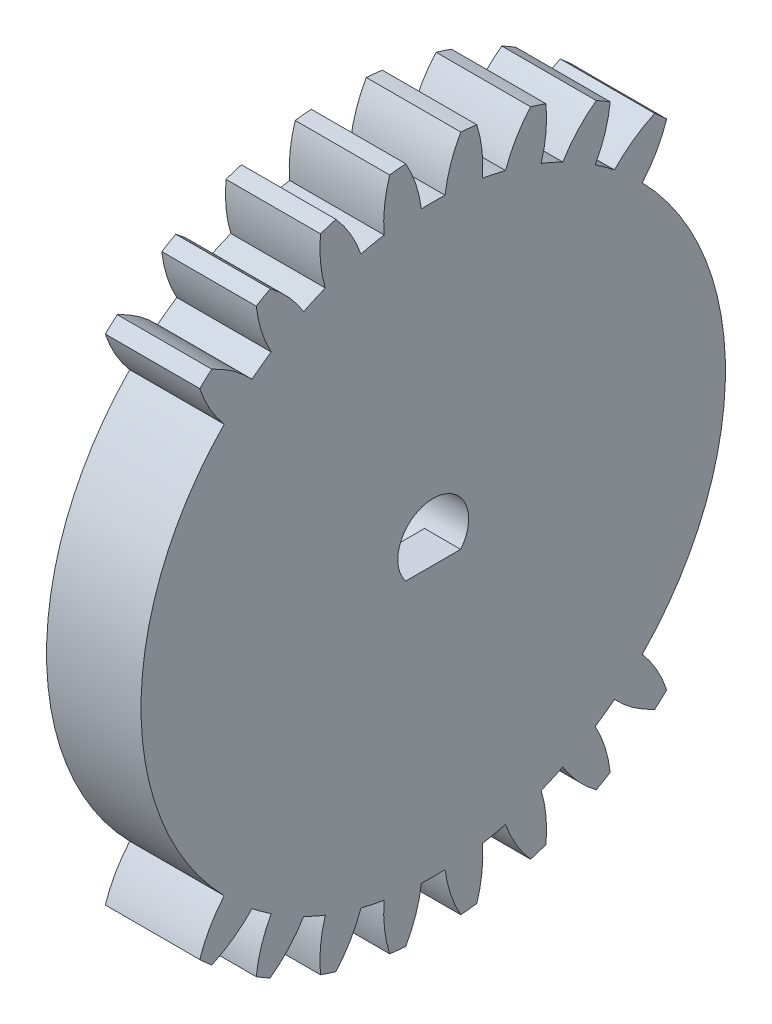
SolidWorks part; units mm, degrees
ref_plane "Plane1" through (0, 0, 0) normal (0, 0, 1) x (1, 0, 0)
ref_plane "Plane2" through (0, 0, 0) normal (0, 1, 0) x (1, 0, 0)
ref_plane "Plane3" through (0, 0, 0) normal (1, 0, 0) x (0, 0, -1)
other "Configuration Table"
sketch "HoldingSke" plane through (0, 0, 0) normal (0, 1, 0) x (1, 0, 0)
  line L0 (0, 0) -> (1.0373, -0.3982)
  line L1 (-15, 0) -> (100, 0) construction
  line L2 (0, 0) -> (-2.1039, 2.3779)
  line L3 (0, 0) -> (-11.863, 4.5341)
  line L4 (0, 0) -> (7.479, 4.318)
  line L5 (0, 0) -> (-46.8476, -17.4728)
  line L6 (0, 0) -> (-8.2896, -5.593)
  line L7 (-2.1039, 2.3779) -> (8.6586, 51.2059)
  line L8 (-76.2, 54.61) -> (-75.5, 54.61)
  line L9 (-67.7845, 28.3722) -> (-49.3413, 33.142)
  line L10 (-76.2, 71.12) -> (104.1128, 71.12)
  line L11 (0, 0) -> (-10, 0)
  line L12 (-76.2, 101.6) -> (-76.166, 101.6)
  line L13 (24.9733, 27.94) -> (52.9518, 28.4284)
  line L14 (24.9733, 27.94) -> (24.9743, 27.94)
  line L15 (24.9733, 27.94) -> (100.4006, 29.5858)
  line L16 (-63.627, -0.9) -> (-12.827, -0.9)
  circle A0 centre (0, 0) radius 2
  circle A1 centre (0, 0) radius 12.374
  circle A2 centre (0, 0) radius 37.5
  circle A3 centre (0, 0) radius 2
  dimension "Num_teeth" = 30
  dimension "Pitch_radius" = 180.3128
  dimension "Width" = 10
  dimension "Thickness" = 10
sketch "BasProSke" plane through (0, 0, 0) normal (0, 1, 0) x (1, 0, 0)
  line L0 (-10, 0) -> (60, 0) construction
  line L1 (0, 0) -> (0, 14.4)
  line L2 (0, 0) -> (4, 0)
  line L3 (4, 0) -> (4, 14.4)
  line L4 (4, 14.4) -> (0, 14.4)
  dimension "Diameter" = 28.8
  dimension "D1" = 4
revolve "Base-Revolve" add sketch "BasProSke" angle 360 about L0
sketch "TooCutSke" plane through (0, 0, 0) normal (1, 0, 0) x (0, 0, -1)
  line L1 (0, 0) -> (0, 107) construction
  line L2 (0, 0) -> (-0.766, 13.4782) construction
  line L3 (0, 0) -> (-2.819, 26.8212) construction
  line L4 (-0.766, 13.4782) -> (-1.4095, 13.4106) construction
  arc A0 (0.502, 12.3638) -> (-0.502, 12.3638) centre (0, 0) ccw
  arc A1 (1.1789, 14.3771) -> (-1.1789, 14.3771) centre (0, 0) ccw
  circle A2 centre (0, 0) radius 13.5 construction
  circle A3 centre (0, 0) radius 13.07 construction
  arc A4 (-0.502, 12.3638) -> (-1.1789, 14.3771) centre (-5.8589, 11.6832) ccw
  arc A5 (1.1789, 14.3771) -> (0.502, 12.3638) centre (5.8589, 11.6832) ccw
extrude "ToothCut" cut sketch "TooCutSke" along normal through all
fillet "Breaks" [suppressed] radius 0.018 tangent propagation no
fillet "RootFillets" [suppressed] radius 0.226
pattern_circular "TeethCuts" count 30 every 12 about axis through (-10, 0, 0) along (1, 0, 0) of "ToothCut"
sketch "HubNeaOneSke" plane through (0, 0, 0) normal (-1, 0, 0) x (0, 0, 1)
  circle A0 centre (0, 0) radius 12.374
  dimension "Diameter" = 24.748
extrude "HubNearOne" [suppressed] add sketch "HubNeaOneSke" along normal blind 40.0001
sketch "HubNeaBotSke" plane through (0, 0, 0) normal (-1, 0, 0) x (0, 0, 1)
  circle A0 centre (0, 0) radius 12.374
  dimension "Diameter" = 24.748
extrude "HubNearBoth" [suppressed] add sketch "HubNeaBotSke" along normal blind 20
ref_plane "FarPln" through (10, 0, 0) normal (1, 0, 0) x (0, 0, -1)
sketch "HubFarSke" plane through (10, 0, 0) normal (1, 0, 0) x (0, 0, -1)
  circle A0 centre (0, 0) radius 12.374
  dimension "Diameter" = 24.748
extrude "HubFar" [suppressed] add sketch "HubFarSke" along normal blind 20
sketch "BorSke" plane through (0, 0, 0) normal (1, 0, 0) x (0, 0, -1)
  line L0 (-1.1608, -0.95) -> (1.1608, -0.95)
  line L1 (0, 1.5) -> (0, -0.95) construction
  arc A0 (1.1608, -0.95) -> (-1.1608, -0.95) centre (0, 0) ccw
  dimension "D1" = 2.45
  dimension "Diameter" = 3
extrude "Bore" cut sketch "BorSke" along normal mid plane 100.0001
sketch "KeySke" plane through (0, 0, 0) normal (1, 0, 0) x (0, 0, -1)
  line L0 (-0.8, 0) -> (-0.8, 2.7)
  line L1 (-0.8, 2.7) -> (0.8, 2.7)
  line L2 (0.8, 2.7) -> (0.8, 0)
  line L3 (0, 0) -> (0, 34) construction
  line L4 (-0.8, 0) -> (0.8, 0)
  dimension "Width" = 1.6
extrude "Keyway" [suppressed] cut sketch "KeySke" along normal mid plane 100.0001
pattern_circular "Keyway2" [suppressed] count 2 every 90 about axis through (-10, 0, 0) along (1, 0, 0)
sketch "Sketch1" plane through (4, 0, 0) normal (1, 0, 0) x (0, 0, -1)
  line L4 (0, 12.374) -> (0, -12.374) construction
  line L9 (-9.1957, 8.2798) -> (-11.8374, 9.9904)
  line L10 (-9.0832, -8.4031) -> (-11.109, -10.7946)
  line L11 (9.0832, -8.4031) -> (11.109, -10.7946)
  line L12 (9.1957, 8.2798) -> (11.8374, 9.9904)
  arc A11 (0.502, 12.3638) -> (-0.502, 12.3638) centre (0, 0) ccw construction
  arc A12 (-0.502, -12.3638) -> (0.502, -12.3638) centre (0, 0) ccw construction
  arc A14 (-9.1957, 8.2798) -> (-9.0832, -8.4031) centre (0, 0) ccw
  arc A15 (-10.4564, 6.6167) -> (-10.9584, 5.7472) centre (0, 0) ccw construction
  arc A16 (-11.109, -10.7946) -> (-11.8374, 9.9904) centre (0, 0) cw
  arc A17 (-8.8522, 8.6461) -> (-9.524, 7.8999) centre (0, 0) ccw construction
  arc A18 (11.109, -10.7946) -> (11.8374, 9.9904) centre (0, 0) ccw
  arc A19 (9.1957, 8.2798) -> (9.0832, -8.4031) centre (0, 0) cw
  point P9 (0, 0)
  point P11 (-9.0832, -8.4031)
  point P13 (0, 0)
  point P20 (-10.9357, -10.59)
  point P21 (-9.1957, 8.2798)
  point P25 (-11.8374, 9.9904)
extrude "Cut-Extrude2" cut sketch "Sketch1" against normal blind 10
sketch "Sketch3" plane through (0, 0, 0) normal (-1, 0, 0) x (0, 0, 1)
  circle A2 centre (0, 0) radius 1.5
  dimension "D1" = 3
extrude "Cut-Extrude3" cut sketch "Sketch3" against normal blind 2.47
equation "' \"Module@HoldingSke\" = 6.35"
equation "' \"Num_teeth@HoldingSke\" = 12"
equation "' \"Ap@HoldingSke\" =  20"
equation "' \"Ap@HoldingSke\" = 20"
equation "' \"Width@HoldingSke\" = 0.5 * 25.4"
equation "' \"Hub_dia@HoldingSke\"= 1 * 25.4"
equation "' \"Hub_dia@HoldingSke\" = 1 * 25.4"
equation "' \"Overall_len@HoldingSke\" = 1.0 * 25.4"
equation "' \"Bore@HoldingSke\" = 0.75 * 25.4"
equation "' \"T_dim@HoldingSke\" = 0.1 * 25.4"
equation "' \"Width@KeySke\" = 0.25 * 25.4"
equation "' \"Show_teeth@HoldingSke\" = 13"
equation "' \"Backlash@HoldingSke\" = 0.009 * 25.4"
equation "' \"Addendum_fac@HoldingSke\" = 1.0"
equation "' \"Dedendum_fac@HoldingSke\" = 1.25"
equation "' \"Dedendum_add@HoldingSke\" = 0.00005 * 25.4"
equation "' \"Clearance_fac@HoldingSke\" = 0.25"
equation "\"Pitch@HoldingSke\" = 1 / \"Module@HoldingSke\""
equation "\"Overcut_dia@TooCutSke\" = (\"Num_teeth@HoldingSke\" + 2 * \"Addendum_fac@HoldingSke\") / \"Pitch@HoldingSke\" + 0.002 * 25.4"
equation "\"Pitch_dia@TooCutSke\" = \"Num_teeth@HoldingSke\" / \"Pitch@HoldingSke\""
equation "\"Base_dia@TooCutSke\" = \"Num_teeth@HoldingSke\" / \"Pitch@HoldingSke\" * cos((\"Ap@HoldingSke\"  * 3.14159265 / 180))"
equation "\"Root_dia@TooCutSke\" = (\"Num_teeth@HoldingSke\" + 2) / \"Pitch@HoldingSke\" - 2 * (\"Addendum_fac@HoldingSke\" + \"Dedendum_fac@HoldingSke\") / \"Pitch@HoldingSke\" - \"Dedendum_add@HoldingSke\" * 2"
equation "\"Half_ang@TooCutSke\" = 180 / \"Num_teeth@HoldingSke\""
equation "\"Half_CT@TooCutSke\" = \"Num_teeth@HoldingSke\" / \"Pitch@HoldingSke\" * sin((3.14159265 / 2 / \"Num_teeth@HoldingSke\")) / 2 - 7 * \"Backlash@HoldingSke\" / 4"
equation "\"Flank_rad@TooCutSke\" = \"Num_teeth@HoldingSke\" / \"Pitch@HoldingSke\" / 5"
equation "\"Radius@RootFillets\" = \"Clearance_fac@HoldingSke\" / \"Pitch@HoldingSke\" + \"Dedendum_add@HoldingSke\""
equation "\"Break_rad@Breaks\" = 0.02 / \"Pitch@HoldingSke\""
equation "\"Thickness@HoldingSke\" = \"Width@HoldingSke\""
equation "\"OAL@HoldingSke\" = \"Thickness@HoldingSke\""
equation "\"MHD@HoldingSke\" = (\"Num_teeth@HoldingSke\" + 2) / \"Pitch@HoldingSke\" - 2 * (\"Addendum_fac@HoldingSke\" + \"Dedendum_fac@HoldingSke\")  / \"Pitch@HoldingSke\" - \"Dedendum_add@HoldingSke\" * 2"
equation "\"MBD@HoldingSke\" = (\"Num_teeth@HoldingSke\" + 2) / \"Pitch@HoldingSke\" - 2 * (\"Addendum_fac@HoldingSke\" + \"Dedendum_fac@HoldingSke\")  / \"Pitch@HoldingSke\" - \"Dedendum_add@HoldingSke\" * 2 - 0.002 * 25.4"
equation "\"MHD@HoldingSke\" = ((sgn( \"MHD@HoldingSke\" - \"Hub_dia@HoldingSke\" )-1)*( \"MHD@HoldingSke\" - \"Hub_dia@HoldingSke\" ))/-2+ \"Hub_dia@HoldingSke\""
equation "\"MBD@HoldingSke\" = ((sgn( \"MBD@HoldingSke\" - \"Bore@HoldingSke\" )-1)*( \"MBD@HoldingSke\" - \"Bore@HoldingSke\" ))/-2+ \"Bore@HoldingSke\""
equation "\"OAL@HoldingSke\" = ((sgn( \"OAL@HoldingSke\" - \"Overall_len@HoldingSke\" )+1)*( \"OAL@HoldingSke\" - \"Overall_len@HoldingSke\" ))/2 + \"Overall_len@HoldingSke\" + 0.000002 * 25.4"
equation "\"Angle@TeethCuts\" = 360.0 / \"Num_teeth@HoldingSke\""
equation "\"Diameter@BasProSke\" = (\"Num_teeth@HoldingSke\" + 2 * \"Addendum_fac@HoldingSke\") / \"Pitch@HoldingSke\""
equation "' \"Fillet_rad@BasProSke\" =  \"Thickness@HoldingSke\" * 0.05"
equation "' \"Fillet_rad@BasProSke\" = \"Thickness@HoldingSke\" * 0.05"
equation "\"MHD@HoldingSke\" = ((sgn( \"MHD@HoldingSke\" - \"Root_dia@TooCutSke\" )-1)*( \"MHD@HoldingSke\" - \"Root_dia@TooCutSke\" ))/-2+ \"Root_dia@TooCutSke\""
equation "\"Diameter@HubNeaOneSke\" = \"MHD@HoldingSke\""
equation "\"Length@HubNearOne\" = \"OAL@HoldingSke\" - \"Thickness@BasProSke\""
equation "\"Diameter@HubNeaBotSke\" = \"MHD@HoldingSke\""
equation "\"Length@HubNearBoth\" = ( \"OAL@HoldingSke\" - \"Thickness@BasProSke\" ) / 2.0"
equation "\"Thickness@FarPln\" = \"Thickness@BasProSke\""
equation "\"Diameter@HubFarSke\" = \"MHD@HoldingSke\""
equation "\"Length@HubFar\" = ( \"OAL@HoldingSke\" - \"Thickness@BasProSke\" ) / 2.0"
equation "\"D1@Bore\" = \"OAL@HoldingSke\" * 2.0"
equation "\"D1@Keyway\" = \"OAL@HoldingSke\" * 2.0"
equation "\"Offset@KeySke\" = \"T_dim@HoldingSke\" + \"MBD@HoldingSke\" / 2.0"
